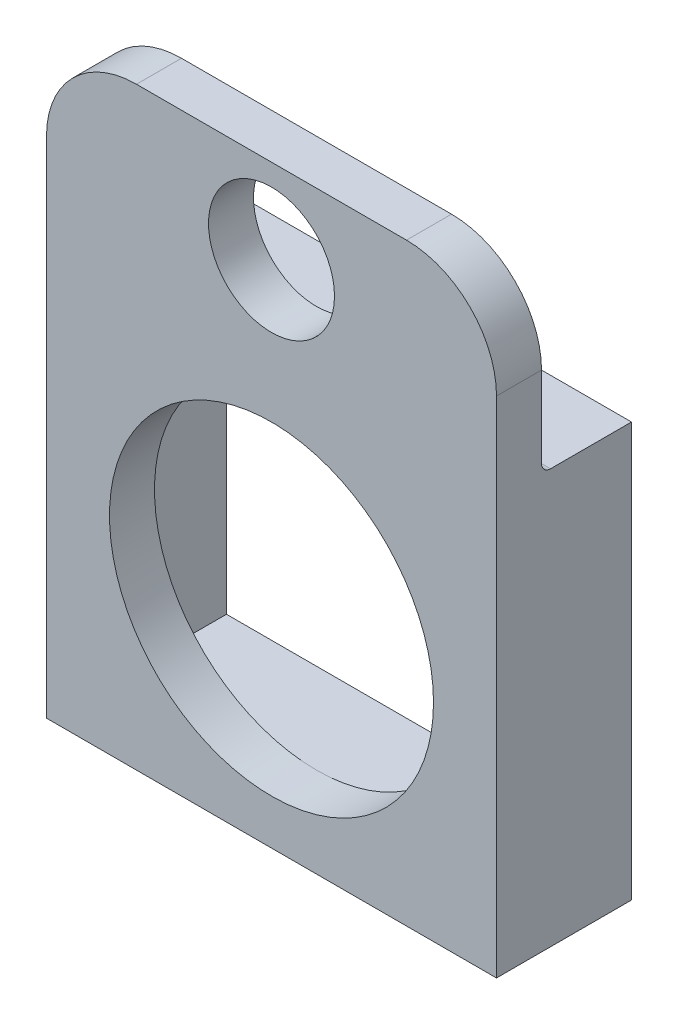
SolidWorks part; units mm, degrees
ref_plane "Front Plane" through (0, 0, 0) normal (0, 0, 1) x (1, 0, 0)
ref_plane "Top Plane" through (0, 0, 0) normal (0, 1, 0) x (1, 0, 0)
ref_plane "Right Plane" through (0, 0, 0) normal (1, 0, 0) x (0, 0, -1)
sketch "Sketch1" plane through (0, 0, 0) normal (0, 0, 1) x (1, 0, 0)
  line L1 (-22.1127, 40.5634) -> (27.8873, 40.5634)
  line L2 (-22.1127, 40.5634) -> (-22.1127, -5.4366)
  line L3 (-22.1127, -5.4366) -> (27.8873, -5.4366)
  line L4 (27.8873, 40.5634) -> (27.8873, -5.4366)
  dimension "D1" = 50
  dimension "D2" = 46
extrude "Boss-Extrude1" add sketch "Sketch1" along normal blind 15
shell "Shell1" thickness 5 removed face at (2.8873, 17.5634, 0)
sketch "Sketch2" plane through (0, 0, 15) normal (0, 0, 1) x (1, 0, 0)
  line L0 (27.8873, -5.4366) -> (27.8873, 40.5634) construction
  line L3 (27.8873, 40.5634) -> (-22.1127, 40.5634) construction
  circle A2 centre (2.8873, 17.5634) radius 18
  dimension "D3" = 36
  dimension "D1" = 25
  dimension "D2" = 23
extrude "Cut-Extrude1" cut sketch "Sketch2" against normal blind 5
sketch "Sketch6" plane through (0, 40.5634, 0) normal (0, 1, 0) x (1, 0, 0)
  line L0 (-22.1127, -15) -> (-22.1127, 0) construction
  line L1 (-22.1127, -10) -> (27.8873, -10)
  line L2 (-22.1127, -10) -> (-22.1127, -15)
  line L3 (-22.1127, -15) -> (27.8873, -15)
  line L4 (27.8873, -10) -> (27.8873, -15)
  line L5 (27.8873, -15) -> (27.8873, 0) construction
  line L6 (27.8873, -15) -> (-22.1127, -15) construction
  dimension "D1" = 5
extrude "Boss-Extrude4" add sketch "Sketch6" along normal blind 20
fillet "Fillet2" radius 10 2 edges at (-22.1127, 60.5634, 12.5) (27.8873, 60.5634, 12.5)
sketch "Sketch7" plane through (0, 0, 15) normal (0, 0, 1) x (1, 0, 0)
  line L0 (27.8873, -5.4366) -> (27.8873, 50.5634) construction
  circle A0 centre (2.8873, 51.1738) radius 7
  dimension "D2" = 14
  dimension "D1" = 25
extrude "Cut-Extrude5" cut sketch "Sketch7" against normal blind 20
fillet "Fillet3" radius 1 1 edges at (2.8873, 40.5634, 10)
